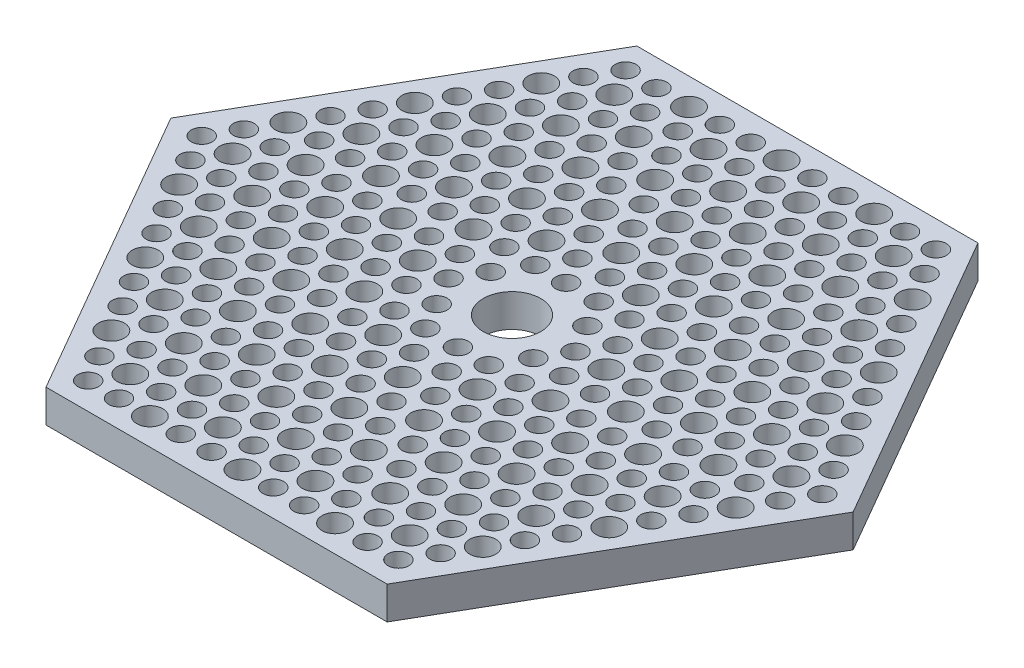
SolidWorks part; units mm, degrees
material "IG-110 Graphite"
ref_plane "Front Plane" through (0, 0, 0) normal (0, 0, 1) x (1, 0, 0)
ref_plane "Top Plane" through (0, 0, 0) normal (0, 1, 0) x (1, 0, 0)
ref_plane "Right Plane" through (0, 0, 0) normal (1, 0, 0) x (0, 0, -1)
sketch "Sketch1" plane through (0, 0, 0) normal (0, 1, 0) x (1, 0, 0)
  line L0 (103.923, 180) -> (-103.923, -180) construction
  line L5 (-207.8461, 0) -> (-103.923, -180)
  line L6 (-103.923, -180) -> (103.923, -180)
  line L7 (103.923, -180) -> (207.8461, 0)
  line L8 (207.8461, 0) -> (103.923, 180)
  line L9 (103.923, 180) -> (-103.923, 180)
  line L10 (-103.923, 180) -> (-207.8461, 0)
  line L11 (103.923, -180) -> (-103.923, 180) construction
  line L12 (-207.8461, 0) -> (207.8461, 0) construction
  line L13 (-75.723, -131.1562) -> (-47.523, -82.3123) construction
  line L14 (-85.123, -147.4374) -> (-66.323, -147.4374) construction
  line L15 (-85.123, -147.4374) -> (-94.523, -131.1562) construction
  line L16 (-85.123, -147.4374) -> (-28.723, -147.4374) construction
  line L17 (-56.923, -98.5936) -> (-38.123, -98.5936) construction
  line L18 (-56.923, -98.5936) -> (-0.523, -98.5936) construction
  line L19 (-47.523, -49.7498) -> (-38.123, -33.4685) construction
  line L20 (-38.123, -33.4685) -> (-28.723, -17.1872) construction
  line L21 (-47.523, -114.8749) -> (-38.123, -98.5936) construction
  line L22 (-28.723, -17.1872) -> (-113.323, -163.7187) construction
  line L23 (-113.323, -163.7187) -> (55.877, -163.7187) construction
  line L24 (55.877, -163.7187) -> (-28.723, -17.1872) construction
  line L25 (-38.123, -98.5936) -> (-28.723, -82.3123) construction
  line L27 (-28.723, -82.3123) -> (-56.923, -131.1562) construction
  line L28 (-56.923, -131.1562) -> (-0.523, -131.1562) construction
  line L29 (-0.523, -131.1562) -> (-28.723, -82.3123) construction
  circle A1 centre (0, 0) radius 180 construction
  circle A12 centre (-94.523, -163.7187) radius 6.35
  circle A13 centre (-85.123, -147.4374) radius 7.94
  circle A22 centre (-103.923, -147.4374) radius 6.35
  circle A23 centre (-94.523, -131.1562) radius 6.35
  circle A24 centre (-75.723, -131.1562) radius 6.35
  circle A25 centre (-66.323, -147.4374) radius 6.35
  circle A26 centre (-75.723, -163.7187) radius 6.35
  circle A27 centre (-47.523, -82.3123) radius 6.35
  circle A28 centre (-38.123, -98.5936) radius 6.35
  circle A29 centre (-66.323, -82.3123) radius 6.35
  circle A30 centre (-75.723, -98.5936) radius 6.35
  circle A31 centre (-56.923, -98.5936) radius 7.94
  circle A32 centre (-66.323, -114.8749) radius 6.35
  circle A33 centre (-47.523, -114.8749) radius 6.35
  circle A34 centre (-19.323, -33.4685) radius 6.35
  circle A35 centre (-9.923, -49.7498) radius 6.35
  circle A36 centre (-38.123, -33.4685) radius 6.35
  circle A37 centre (-47.523, -49.7498) radius 6.35
  circle A38 centre (-28.723, -49.7498) radius 7.94
  circle A39 centre (-38.123, -66.0311) radius 6.35
  circle A40 centre (-19.323, -66.0311) radius 6.35
  circle A41 centre (-28.723, -147.4374) radius 7.94
  circle A42 centre (-9.923, -147.4374) radius 6.35
  circle A43 centre (-19.323, -163.7187) radius 6.35
  circle A44 centre (-38.123, -163.7187) radius 6.35
  circle A45 centre (-47.523, -147.4374) radius 6.35
  circle A46 centre (-38.123, -131.1562) radius 6.35
  circle A47 centre (-19.323, -131.1562) radius 6.35
  circle A48 centre (27.677, -147.4374) radius 7.94
  circle A49 centre (46.477, -147.4374) radius 6.35
  circle A50 centre (37.077, -163.7187) radius 6.35
  circle A51 centre (18.277, -163.7187) radius 6.35
  circle A52 centre (8.877, -147.4374) radius 6.35
  circle A53 centre (18.277, -131.1562) radius 6.35
  circle A54 centre (37.077, -131.1562) radius 6.35
  circle A55 centre (-0.523, -98.5936) radius 7.94
  circle A56 centre (18.277, -98.5936) radius 6.35
  circle A57 centre (8.877, -82.3123) radius 6.35
  circle A58 centre (-9.923, -82.3123) radius 6.35
  circle A59 centre (-19.323, -98.5936) radius 6.35
  circle A60 centre (-9.923, -114.8749) radius 6.35
  circle A61 centre (8.877, -114.8749) radius 6.35
  circle A62 centre (-28.723, -114.8749) radius 48.8438 construction
  circle A63 centre (-28.723, -114.8749) radius 16.2813 construction
  circle A64 centre (-56.923, -131.1562) radius 7.94
  circle A65 centre (-56.923, -163.7187) radius 7.94
  circle A66 centre (-0.523, -163.7187) radius 7.94
  circle A67 centre (55.877, -163.7187) radius 7.94
  circle A68 centre (27.677, -114.8749) radius 7.94
  circle A69 centre (-0.523, -131.1562) radius 7.94
  circle A70 centre (-28.723, -82.3123) radius 7.94
  circle A71 centre (-28.723, -114.8749) radius 7.94
  circle A72 centre (-85.123, -114.8749) radius 7.94
  circle A73 centre (-56.923, -66.0311) radius 7.94
  circle A74 centre (-0.523, -66.0311) radius 7.94
  circle A75 centre (-28.723, -17.1872) radius 6.35
  dimension "D1" = 360
  dimension "D4" = 12.7
  dimension "D5" = 15.88
  dimension "D3" = 18.8
  dimension "D8" = 56.4
  dimension "D10" = 56.4
  dimension "D12" = 56.4
  dimension "D7" = 3
  dimension "D9" = 3
  dimension "D11" = 2
  dimension "D6" = 6
extrude "Boss-Extrude2" add sketch "Sketch1" against normal blind 20 contours L7 L8 L9 L10 L5 L6
extrude "Cut-Extrude3" cut sketch "Sketch1<8>" against normal through all flip side to cut
sketch "Sketch1<8>" plane through (0, 0, 0) normal (0, 1, 0) x (1, 0, 0) same geometry as "Sketch1"
sketch "Sketch3" plane through (0, 0, 0) normal (0, 1, 0) x (1, 0, 0)
  circle A0 centre (0, 0) radius 17.5
  dimension "D1" = 35
extrude "Cut-Extrude4" cut sketch "Sketch3" against normal through all
pattern_circular "CirPattern1" count 6 over 360 about axis through (0, 0, 0) along (0, 1, 0) of "Cut-Extrude3"
equation "\"TriangularPitch\"= 1.880cm"
equation "\"CoolantHole\"= 1.588cm"
equation "\"FuelHole\"= 1.27cm"
equation "\"D4@Sketch1\"=\"FuelHole\""
equation "\"D5@Sketch1\"=\"CoolantHole\""
equation "\"D3@Sketch1\"=\"TriangularPitch\""
equation "\"D8@Sketch1\"=\"TriangularPitch\"*3"
equation "\"D10@Sketch1\"=\"TriangularPitch\"*3"
equation "\"D12@Sketch1\"=\"TriangularPitch\"*3"
equation "\"CenterHole\"= 3.5cm"
equation "\"HexagonSize\"= 36cm"
equation "\"D1@Sketch3\"=\"CenterHole\""
equation "\"D1@Sketch1\"=\"HexagonSize\""
